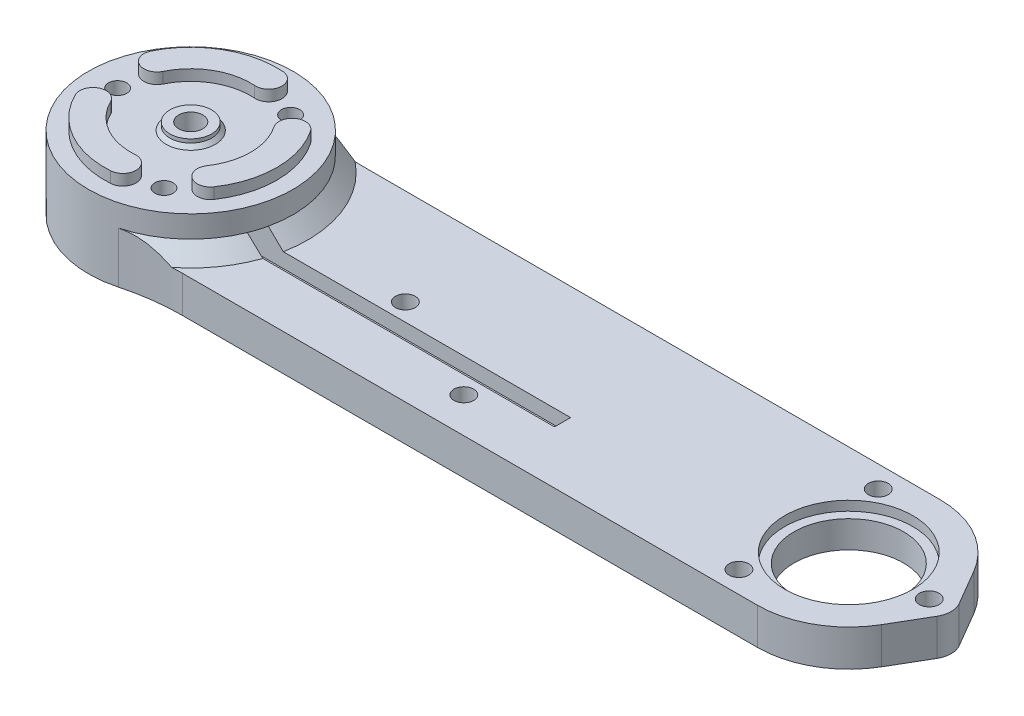
SolidWorks part; units mm, degrees
ref_plane "前视基准面" through (0, 0, 0) normal (0, 0, 1) x (1, 0, 0)
ref_plane "上视基准面" through (0, 0, 0) normal (0, 1, 0) x (1, 0, 0)
ref_plane "右视基准面" through (0, 0, 0) normal (1, 0, 0) x (0, 0, -1)
sketch "草图1" plane through (0, 0, 0) normal (0, 1, 0) x (1, 0, 0)
  line L0 (45, 0) -> (-45, 0) construction
  line L1 (45, -12.5) -> (-45, -12.5)
  line L2 (45, 12.5) -> (-45, 12.5)
  arc A0 (45, -12.5) -> (45, 12.5) centre (45, 0) ccw
  arc A1 (-45, 12.5) -> (-45, -12.5) centre (-45, 0) ccw
  point P2 (0, 0)
  dimension "D2" = 12.5
  dimension "D1" = 90
extrude "凸台-拉伸1" add sketch "草图1" along normal blind 5
sketch "草图3" plane through (0, 0, 0) normal (0, 1, 0) x (1, 0, 0)
  circle A0 centre (-45, 0) radius 14
  dimension "D1" = 28
extrude "凸台-拉伸2" add sketch "草图3" along normal blind 10
sketch "草图5" plane through (0, 10, 0) normal (0, 1, 0) x (1, 0, 0)
  line L0 (-45, 0) -> (-55, 0) construction
  line L1 (-45, 0) -> (-40, 8.6603) construction
  line L2 (-45, 0) -> (-40, -8.6603) construction
  circle A0 centre (-45, 0) radius 10 construction
  circle A1 centre (-55, 0) radius 1.25
  circle A2 centre (-40, 8.6603) radius 1.25
  circle A3 centre (-40, -8.6603) radius 1.25
  dimension "D1" = 20
  dimension "D4" = 2.5
  dimension "D2" = 120
  dimension "D3" = 120
extrude "切除-拉伸2" cut sketch "草图5" against normal up to next
sketch "草图6" plane through (0, 0, 0) normal (0, -1, 0) x (1, 0, 0)
  circle A0 centre (-55, 0) radius 2.75
  circle A1 centre (-40, 8.6603) radius 2.75
  circle A2 centre (-40, -8.6603) radius 2.75
  dimension "D1" = 5.5
fillet "圆角1" radius 30 2 edges at (-38.6952, 2.5, -12.5) (-38.6952, 2.5, 12.5)
extrude "切除-拉伸3" cut sketch "草图6" against normal blind 5
sketch "草图7" plane through (0, 10, 0) normal (0, 1, 0) x (1, 0, 0)
  line L0 (-45, 0) -> (-35, 0) construction
  line L1 (-45, 0) -> (-50, 8.6603) construction
  line L2 (-45, 0) -> (-50, -8.6603) construction
  line L3 (-45, 0) -> (-44.3024, -9.9756) construction
  circle A0 centre (-45, 0) radius 10 construction
  arc A1 (-53.9879, 4.3837) -> (-44.3024, 9.9756) centre (-45, 0) cw construction
  arc A2 (-44.1769, 11.7713) -> (-55.6058, 5.1728) centre (-45, 0) ccw
  arc A3 (-44.428, 8.18) -> (-52.3701, 3.5946) centre (-45, 0) ccw
  arc A4 (-44.428, 8.18) -> (-44.1769, 11.7713) centre (-44.3024, 9.9756) ccw
  arc A5 (-55.6058, 5.1728) -> (-52.3701, 3.5946) centre (-53.9879, 4.3837) ccw
  arc A6 (-53.9879, -4.3837) -> (-44.3024, -9.9756) centre (-45, 0) ccw construction
  arc A7 (-55.6058, -5.1728) -> (-44.1769, -11.7713) centre (-45, 0) ccw
  arc A8 (-52.3701, -3.5946) -> (-44.428, -8.18) centre (-45, 0) ccw
  arc A9 (-52.3701, -3.5946) -> (-55.6058, -5.1728) centre (-53.9879, -4.3837) ccw
  arc A10 (-44.1769, -11.7713) -> (-44.428, -8.18) centre (-44.3024, -9.9756) ccw
  arc A11 (-36.7096, -5.5919) -> (-36.7096, 5.5919) centre (-45, 0) ccw construction
  arc A12 (-35.2174, -6.5985) -> (-35.2174, 6.5985) centre (-45, 0) ccw
  arc A13 (-38.2019, -4.5854) -> (-38.2019, 4.5854) centre (-45, 0) ccw
  arc A14 (-38.2019, -4.5854) -> (-35.2174, -6.5985) centre (-36.7096, -5.5919) ccw
  arc A15 (-35.2174, 6.5985) -> (-38.2019, 4.5854) centre (-36.7096, 5.5919) ccw
  point P6 (-50, 8.6603)
  point P11 (-50, -8.6603)
  point P19 (-35, 0)
  dimension "D1" = 20
  dimension "D5" = 1.8
  dimension "D2" = 34
  dimension "D3" = 120
  dimension "D4" = 120
extrude "凸台-拉伸3" add sketch "草图7" along normal blind 1.5
sketch "草图8" plane through (0, 10, 0) normal (0, 1, 0) x (1, 0, 0)
  circle A0 centre (-45, 0) radius 2.85
  dimension "D1" = 5.7
extrude "凸台-拉伸4" add sketch "草图8" along normal blind 1
chamfer "倒角2" distance 0.5 angle 45 1 edges at (-45, 10, 2.85)
sketch "草图9" plane through (0, 5, 0) normal (0, -1, 0) x (1, 0, 0)
  line L1 (-56.25, 2.4495) -> (-57.75, 2.4495)
  line L6 (-56.25, 2.4495) -> (-56.25, -2.4495)
  line L7 (-56.25, -2.4495) -> (-57.75, -2.4495)
  line L12 (-57.75, 2.4495) -> (-57.75, -2.4495)
  line L13 (-53.75, 2.4495) -> (-52.25, 2.4495)
  line L14 (-53.75, 2.4495) -> (-53.75, -2.4495)
  line L15 (-42.75, 11.1097) -> (-41.25, 11.1097)
  line L16 (-42.75, 11.1097) -> (-42.75, 6.2108)
  line L17 (-42.75, 6.2108) -> (-41.25, 6.2108)
  line L18 (-41.25, 11.1097) -> (-41.25, 6.2108)
  line L19 (-37.25, 11.1097) -> (-38.75, 11.1097)
  line L20 (-37.25, 11.1097) -> (-37.25, 6.2108)
  line L21 (-37.25, 6.2108) -> (-38.75, 6.2108)
  line L22 (-38.75, 11.1097) -> (-38.75, 6.2108)
  line L23 (-42.75, -6.2108) -> (-41.25, -6.2108)
  line L24 (-42.75, -6.2108) -> (-42.75, -11.1097)
  line L25 (-42.75, -11.1097) -> (-41.25, -11.1097)
  line L26 (-41.25, -6.2108) -> (-41.25, -11.1097)
  line L27 (-37.25, -6.2108) -> (-38.75, -6.2108)
  line L28 (-37.25, -6.2108) -> (-37.25, -11.1097)
  line L29 (-37.25, -11.1097) -> (-38.75, -11.1097)
  line L30 (-38.75, -6.2108) -> (-38.75, -11.1097)
  line L31 (-53.75, -2.4495) -> (-52.25, -2.4495)
  line L32 (-52.25, 2.4495) -> (-52.25, -2.4495)
  circle A3 centre (-40, -8.6603) radius 2.75 construction
  circle A4 centre (-40, -8.6603) radius 1.25 construction
  circle A5 centre (-40, -8.6603) radius 2.75 construction
  circle A6 centre (-40, 8.6603) radius 2.75 construction
  circle A7 centre (-40, 8.6603) radius 1.25 construction
  circle A8 centre (-40, 8.6603) radius 2.75 construction
  circle A9 centre (-55, 0) radius 2.75 construction
  circle A10 centre (-55, 0) radius 2.75 construction
  circle A11 centre (-55, 0) radius 1.25 construction
extrude "凸台-拉伸5" [suppressed] add sketch "草图9" along normal blind 0.2
chamfer "倒角3" distance 2 angle 45 1 edges at (-31, 5, 0)
sketch "草图11" plane through (0, 0, 0) normal (0, 1, 0) x (1, 0, 0)
  line L0 (57.5, 0) -> (56, 0) construction
  line L1 (58.5909, 1.5123) -> (55.7955, 6.3014)
  line L2 (55.7955, 6.3014) -> (55.7955, -6.3014)
  line L3 (55.7955, -6.3014) -> (58.5909, -1.5123)
  arc A0 (45, -12.5) -> (45, 12.5) centre (45, 0) ccw construction
  circle A1 centre (56, 0) radius 3 construction
  arc A2 (58.5909, 1.5123) -> (58.5909, -1.5123) centre (56, 0) cw
  dimension "D2" = 6
  dimension "D1" = 1.5
extrude "凸台-拉伸6" add sketch "草图11" along normal up to surface (5 mm away) up to face at (-4.7959, 5, 0)
sketch "草图10" plane through (0, 5, 0) normal (0, 1, 0) x (1, 0, 0)
  circle A0 centre (45, 0) radius 7.5
  dimension "D1" = 15
extrude "切除-拉伸5" cut sketch "草图10" against normal up to next
sketch "草图12" plane through (0, 5, 0) normal (0, 1, 0) x (1, 0, 0)
  circle A0 centre (45, 0) radius 8.75
  dimension "D1" = 17.5
extrude "切除-拉伸6" cut sketch "草图12" against normal blind 1.3
sketch "草图13" plane through (0, 5, 0) normal (0, 1, 0) x (1, 0, 0)
  circle A0 centre (45, 0) radius 11 construction
  circle A1 centre (56, 0) radius 1.35
  circle A2 centre (39.5, -9.5263) radius 1.35
  circle A3 centre (39.5, 9.5263) radius 1.35
  point P12 (45, 0)
  dimension "D1" = 22
  dimension "D2" = 2.7
  dimension "D3" = 3
extrude "切除-拉伸7" cut sketch "草图13" against normal up to next
sketch "草图14" plane through (0, 0, 0) normal (0, -1, 0) x (1, 0, 0)
  circle A0 centre (-45, 0) radius 5.25
  dimension "D1" = 10.5
extrude "切除-拉伸8" cut sketch "草图14" against normal blind 5
sketch "草图15" plane through (0, 5, 0) normal (0, -1, 0) x (1, 0, 0)
  line L0 (-45, 0) -> (-50.25, 0) construction
  line L1 (-45, 0) -> (-45, 5.25) construction
  line L4 (-45, 5.25) -> (10, 5.25)
  line L5 (10, 5.25) -> (10, 3.05)
  line L6 (10, 3.05) -> (-40.7268, 3.05)
  line L7 (-40.7268, 3.05) -> (-45, 5.25)
  circle A5 centre (-45, 0) radius 5.25 construction
  circle A6 centre (-45, 0) radius 5.25 construction
  dimension "D1" = 90
  dimension "D2" = 55
  dimension "D3" = 2.2
extrude "切除-拉伸9" cut sketch "草图15" along normal offset from surface (2 mm away) 2 up to face at (56, 5, 1.35)
chamfer "倒角4" distance 2 distance2 8 1 edges at (-42.5969, 3, 4.6677) first distance on face at (-45, 0, -5.25)
sketch "草图16" plane through (0, 5, 0) normal (0, 1, 0) x (1, 0, 0)
  line L0 (-29.2934, -3.05) -> (-31.3363, -3.05)
  line L1 (-29.8859, -5.25) -> (-32.0217, -5.25)
  arc A0 (-41.3757, -13.5227) -> (-41.3757, 13.5227) centre (-45, 0) ccw construction
  circle A1 centre (-45, 0) radius 14 construction
  arc A2 (-29.8859, -5.25) -> (-29.2934, -3.05) centre (-45, 0) ccw
  arc A3 (-32.0217, -5.25) -> (-31.3363, -3.05) centre (-45, 0) ccw
  arc A4 (-29.2934, -3.05) -> (-35.0564, 12.5349) centre (-45, 0) ccw construction
extrude "切除-拉伸10" cut sketch "草图16" along normal up to next
chamfer "倒角5" distance 2 distance2 8 1 edges at (-31.6336, 5, 4.1641) first distance on face at (-45, 10, 14)
sketch "草图17" plane through (0, 5, 0) normal (0, 1, 0) x (1, 0, 0)
  line L0 (10, -4.15) -> (-31.6292, -4.15) construction
  line L1 (10, -5.25) -> (10, -3.05) construction
  line L2 (0, -4.15) -> (0, -7.65) construction
  line L3 (-15, -4.15) -> (-15, -0.65) construction
  line L4 (10, -3.05) -> (10, -5.25) construction
  circle A0 centre (-45, 0) radius 14 construction
  circle A1 centre (-15, -0.65) radius 1.35
  circle A2 centre (0, -7.65) radius 1.35
  dimension "D4" = 2.7
  dimension "D1" = 3.5
  dimension "D2" = 10
  dimension "D3" = 25
extrude "切除-拉伸11" cut sketch "草图17" against normal up to next
sketch "草图18" plane through (0, 5, 0) normal (0, -1, 0) x (1, 0, 0)
  circle A0 centre (-45, 0) radius 1.65
  dimension "D1" = 3.3
extrude "切除-拉伸12" cut sketch "草图18" against normal up to next
